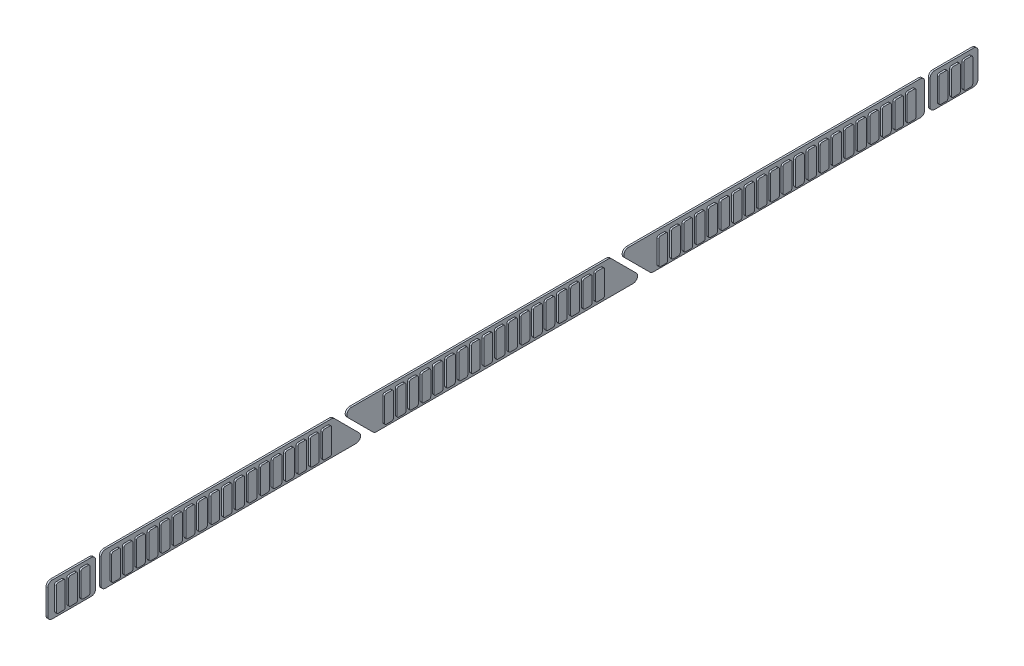
SolidWorks part; units mm, degrees
material "moto_reflective"
ref_plane "Front Plane" through (0, 0, 0) normal (0, 0, 1) x (1, 0, 0)
ref_plane "Top Plane" through (0, 0, 0) normal (0, 1, 0) x (1, 0, 0)
ref_plane "Right Plane" through (0, 0, 0) normal (1, 0, 0) x (0, 0, -1)
sketch "Sketch1" plane through (0, 0, 0) normal (1, 0, 0) x (0, 0, -1)
  line L0 (-262, -7) -> (-262, 7)
  line L5 (-237.5, 9.5) -> (-259.5, 9.5)
  line L6 (-259.5, -9.5) -> (-237.5, -9.5)
  line L8 (262, -7) -> (262, 7)
  line L10 (-232, 7) -> (-232, -7)
  line L11 (-235, 7) -> (-235, -7)
  line L12 (-76.9645, -9.5) -> (67.7218, -9.5)
  line L13 (235, 7) -> (235, -7)
  line L14 (232, 7) -> (232, -7)
  line L15 (-92.7322, 5.2322) -> (-78.7322, -8.7678)
  line L16 (63.2678, 5.2322) -> (77.2678, -8.7678)
  line L17 (-86.5104, -5.2322) -> (-100.5104, 8.7678)
  line L18 (55.4896, 8.7678) -> (69.4896, -5.2322)
  line L19 (-229.5, 9.5) -> (-102.2782, 9.5)
  line L20 (-232, 9.5) -> (-232, -9.5) construction
  line L21 (-235, 9.5) -> (-235, -9.5) construction
  line L25 (-88.2782, -9.5) -> (-229.5, -9.5)
  line L26 (-90.9645, 9.5) -> (53.7218, 9.5)
  line L27 (229.5, 9.5) -> (65.0355, 9.5)
  line L28 (79.0355, -9.5) -> (229.5, -9.5)
  line L29 (259.5, 9.5) -> (237.5, 9.5)
  line L30 (237.5, -9.5) -> (259.5, -9.5)
  line L130 (-257.1932, 7.5778) -> (-254.1932, 7.5778)
  line L131 (-258.1932, 6.5778) -> (-258.1932, -6.4222)
  line L132 (-257.1932, -7.4222) -> (-254.1932, -7.4222)
  line L133 (-253.1932, 6.5778) -> (-253.1932, -6.4222)
  line L134 (-250.1932, 7.5778) -> (-247.1932, 7.5778)
  line L135 (-251.1932, 6.5778) -> (-251.1932, -6.4222)
  line L136 (-250.1932, -7.4222) -> (-247.1932, -7.4222)
  line L137 (-246.1932, 6.5778) -> (-246.1932, -6.4222)
  line L138 (-243.1932, 7.5778) -> (-240.1932, 7.5778)
  line L139 (-244.1932, 6.5778) -> (-244.1932, -6.4222)
  line L140 (-243.1932, -7.4222) -> (-240.1932, -7.4222)
  line L141 (-239.1932, 6.5778) -> (-239.1932, -6.4222)
  line L142 (-225.9916, 7.1613) -> (-222.9916, 7.1613)
  line L143 (-226.9916, 6.1613) -> (-226.9916, -6.8387)
  line L144 (-225.9916, -7.8387) -> (-222.9916, -7.8387)
  line L145 (-221.9916, 6.1613) -> (-221.9916, -6.8387)
  line L146 (-218.9916, 7.1613) -> (-215.9916, 7.1613)
  line L147 (-219.9916, 6.1613) -> (-219.9916, -6.8387)
  line L148 (-218.9916, -7.8387) -> (-215.9916, -7.8387)
  line L149 (-214.9916, 6.1613) -> (-214.9916, -6.8387)
  line L150 (-211.9916, 7.1613) -> (-208.9916, 7.1613)
  line L151 (-212.9916, 6.1613) -> (-212.9916, -6.8387)
  line L152 (-211.9916, -7.8387) -> (-208.9916, -7.8387)
  line L153 (-207.9916, 6.1613) -> (-207.9916, -6.8387)
  line L154 (-204.9916, 7.1613) -> (-201.9916, 7.1613)
  line L155 (-205.9916, 6.1613) -> (-205.9916, -6.8387)
  line L156 (-204.9916, -7.8387) -> (-201.9916, -7.8387)
  line L157 (-200.9916, 6.1613) -> (-200.9916, -6.8387)
  line L158 (-198.1383, 7.4692) -> (-195.1383, 7.4692)
  line L159 (-199.1383, 6.4692) -> (-199.1383, -6.5308)
  line L160 (-198.1383, -7.5308) -> (-195.1383, -7.5308)
  line L161 (-194.1383, 6.4692) -> (-194.1383, -6.5308)
  line L162 (-191.1383, 7.4692) -> (-188.1383, 7.4692)
  line L163 (-192.1383, 6.4692) -> (-192.1383, -6.5308)
  line L164 (-191.1383, -7.5308) -> (-188.1383, -7.5308)
  line L165 (-187.1383, 6.4692) -> (-187.1383, -6.5308)
  line L166 (-184.1383, 7.4692) -> (-181.1383, 7.4692)
  line L167 (-185.1383, 6.4692) -> (-185.1383, -6.5308)
  line L168 (-184.1383, -7.5308) -> (-181.1383, -7.5308)
  line L169 (-180.1383, 6.4692) -> (-180.1383, -6.5308)
  line L170 (-177.1383, 7.4692) -> (-174.1383, 7.4692)
  line L171 (-178.1383, 6.4692) -> (-178.1383, -6.5308)
  line L172 (-177.1383, -7.5308) -> (-174.1383, -7.5308)
  line L173 (-173.1383, 6.4692) -> (-173.1383, -6.5308)
  line L174 (-170.1383, 7.4692) -> (-167.1383, 7.4692)
  line L175 (-171.1383, 6.4692) -> (-171.1383, -6.5308)
  line L176 (-170.1383, -7.5308) -> (-167.1383, -7.5308)
  line L177 (-166.1383, 6.4692) -> (-166.1383, -6.5308)
  line L178 (-163.1383, 7.4692) -> (-160.1383, 7.4692)
  line L179 (-164.1383, 6.4692) -> (-164.1383, -6.5308)
  line L180 (-163.1383, -7.5308) -> (-160.1383, -7.5308)
  line L181 (-159.1383, 6.4692) -> (-159.1383, -6.5308)
  line L182 (-156.1383, 7.4692) -> (-153.1383, 7.4692)
  line L183 (-157.1383, 6.4692) -> (-157.1383, -6.5308)
  line L184 (-156.1383, -7.5308) -> (-153.1383, -7.5308)
  line L185 (-152.1383, 6.4692) -> (-152.1383, -6.5308)
  line L186 (-149.1383, 7.4692) -> (-146.1383, 7.4692)
  line L187 (-150.1383, 6.4692) -> (-150.1383, -6.5308)
  line L188 (-149.1383, -7.5308) -> (-146.1383, -7.5308)
  line L189 (-145.1383, 6.4692) -> (-145.1383, -6.5308)
  line L190 (-142.1383, 7.4692) -> (-139.1383, 7.4692)
  line L191 (-143.1383, 6.4692) -> (-143.1383, -6.5308)
  line L192 (-142.1383, -7.5308) -> (-139.1383, -7.5308)
  line L193 (-138.1383, 6.4692) -> (-138.1383, -6.5308)
  line L194 (-135.1383, 7.4692) -> (-132.1383, 7.4692)
  line L195 (-136.1383, 6.4692) -> (-136.1383, -6.5308)
  line L196 (-135.1383, -7.5308) -> (-132.1383, -7.5308)
  line L197 (-131.1383, 6.4692) -> (-131.1383, -6.5308)
  line L198 (-128.1383, 7.4692) -> (-125.1383, 7.4692)
  line L199 (-129.1383, 6.4692) -> (-129.1383, -6.5308)
  line L200 (-128.1383, -7.5308) -> (-125.1383, -7.5308)
  line L201 (-124.1383, 6.4692) -> (-124.1383, -6.5308)
  line L202 (-121.1383, 7.4692) -> (-118.1383, 7.4692)
  line L203 (-122.1383, 6.4692) -> (-122.1383, -6.5308)
  line L204 (-121.1383, -7.5308) -> (-118.1383, -7.5308)
  line L205 (-117.1383, 6.4692) -> (-117.1383, -6.5308)
  line L206 (-114.1383, 7.4692) -> (-111.1383, 7.4692)
  line L207 (-115.1383, 6.4692) -> (-115.1383, -6.5308)
  line L208 (-114.1383, -7.5308) -> (-111.1383, -7.5308)
  line L209 (-110.1383, 6.4692) -> (-110.1383, -6.5308)
  line L210 (-107.1383, 7.4692) -> (-104.1383, 7.4692)
  line L211 (-108.1383, 6.4692) -> (-108.1383, -6.5308)
  line L212 (-107.1383, -7.5308) -> (-104.1383, -7.5308)
  line L213 (-103.1383, 6.4692) -> (-103.1383, -6.5308)
  line L222 (-72.2636, 7.3699) -> (-69.2636, 7.3699)
  line L223 (-73.2636, 6.3699) -> (-73.2636, -6.6301)
  line L224 (-72.2636, -7.6301) -> (-69.2636, -7.6301)
  line L225 (-68.2636, 6.3699) -> (-68.2636, -6.6301)
  line L226 (-65.2636, 7.3699) -> (-62.2636, 7.3699)
  line L227 (-66.2636, 6.3699) -> (-66.2636, -6.6301)
  line L228 (-65.2636, -7.6301) -> (-62.2636, -7.6301)
  line L229 (-61.2636, 6.3699) -> (-61.2636, -6.6301)
  line L230 (-58.2636, 7.3699) -> (-55.2636, 7.3699)
  line L231 (-59.2636, 6.3699) -> (-59.2636, -6.6301)
  line L232 (-58.2636, -7.6301) -> (-55.2636, -7.6301)
  line L233 (-54.2636, 6.3699) -> (-54.2636, -6.6301)
  line L234 (-51.2636, 7.3699) -> (-48.2636, 7.3699)
  line L235 (-52.2636, 6.3699) -> (-52.2636, -6.6301)
  line L236 (-51.2636, -7.6301) -> (-48.2636, -7.6301)
  line L237 (-47.2636, 6.3699) -> (-47.2636, -6.6301)
  line L238 (-44.4103, 7.6778) -> (-41.4103, 7.6778)
  line L239 (-45.4103, 6.6778) -> (-45.4103, -6.3222)
  line L240 (-44.4103, -7.3222) -> (-41.4103, -7.3222)
  line L241 (-40.4103, 6.6778) -> (-40.4103, -6.3222)
  line L242 (-37.4103, 7.6778) -> (-34.4103, 7.6778)
  line L243 (-38.4103, 6.6778) -> (-38.4103, -6.3222)
  line L244 (-37.4103, -7.3222) -> (-34.4103, -7.3222)
  line L245 (-33.4103, 6.6778) -> (-33.4103, -6.3222)
  line L246 (-30.4103, 7.6778) -> (-27.4103, 7.6778)
  line L247 (-31.4103, 6.6778) -> (-31.4103, -6.3222)
  line L248 (-30.4103, -7.3222) -> (-27.4103, -7.3222)
  line L249 (-26.4103, 6.6778) -> (-26.4103, -6.3222)
  line L250 (-23.4103, 7.6778) -> (-20.4103, 7.6778)
  line L251 (-24.4103, 6.6778) -> (-24.4103, -6.3222)
  line L252 (-23.4103, -7.3222) -> (-20.4103, -7.3222)
  line L253 (-19.4103, 6.6778) -> (-19.4103, -6.3222)
  line L254 (-16.4103, 7.6778) -> (-13.4103, 7.6778)
  line L255 (-17.4103, 6.6778) -> (-17.4103, -6.3222)
  line L256 (-16.4103, -7.3222) -> (-13.4103, -7.3222)
  line L257 (-12.4103, 6.6778) -> (-12.4103, -6.3222)
  line L258 (-9.4103, 7.6778) -> (-6.4103, 7.6778)
  line L259 (-10.4103, 6.6778) -> (-10.4103, -6.3222)
  line L260 (-9.4103, -7.3222) -> (-6.4103, -7.3222)
  line L261 (-5.4103, 6.6778) -> (-5.4103, -6.3222)
  line L262 (-2.4103, 7.6778) -> (0.5897, 7.6778)
  line L263 (-3.4103, 6.6778) -> (-3.4103, -6.3222)
  line L264 (-2.4103, -7.3222) -> (0.5897, -7.3222)
  line L265 (1.5897, 6.6778) -> (1.5897, -6.3222)
  line L266 (4.5897, 7.6778) -> (7.5897, 7.6778)
  line L267 (3.5897, 6.6778) -> (3.5897, -6.3222)
  line L268 (4.5897, -7.3222) -> (7.5897, -7.3222)
  line L269 (8.5897, 6.6778) -> (8.5897, -6.3222)
  line L270 (11.5897, 7.6778) -> (14.5897, 7.6778)
  line L271 (10.5897, 6.6778) -> (10.5897, -6.3222)
  line L272 (11.5897, -7.3222) -> (14.5897, -7.3222)
  line L273 (15.5897, 6.6778) -> (15.5897, -6.3222)
  line L274 (18.5897, 7.6778) -> (21.5897, 7.6778)
  line L275 (17.5897, 6.6778) -> (17.5897, -6.3222)
  line L276 (18.5897, -7.3222) -> (21.5897, -7.3222)
  line L277 (22.5897, 6.6778) -> (22.5897, -6.3222)
  line L278 (25.5897, 7.6778) -> (28.5897, 7.6778)
  line L279 (24.5897, 6.6778) -> (24.5897, -6.3222)
  line L280 (25.5897, -7.3222) -> (28.5897, -7.3222)
  line L281 (29.5897, 6.6778) -> (29.5897, -6.3222)
  line L282 (32.5897, 7.6778) -> (35.5897, 7.6778)
  line L283 (31.5897, 6.6778) -> (31.5897, -6.3222)
  line L284 (32.5897, -7.3222) -> (35.5897, -7.3222)
  line L285 (36.5897, 6.6778) -> (36.5897, -6.3222)
  line L286 (39.5897, 7.6778) -> (42.5897, 7.6778)
  line L287 (38.5897, 6.6778) -> (38.5897, -6.3222)
  line L288 (39.5897, -7.3222) -> (42.5897, -7.3222)
  line L289 (43.5897, 6.6778) -> (43.5897, -6.3222)
  line L290 (46.5897, 7.6778) -> (49.5897, 7.6778)
  line L291 (45.5897, 6.6778) -> (45.5897, -6.3222)
  line L292 (46.5897, -7.3222) -> (49.5897, -7.3222)
  line L293 (50.5897, 6.6778) -> (50.5897, -6.3222)
  line L366 (89.284, 7.2213) -> (92.284, 7.2213)
  line L367 (88.284, 6.2213) -> (88.284, -6.7787)
  line L368 (89.284, -7.7787) -> (92.284, -7.7787)
  line L369 (93.284, 6.2213) -> (93.284, -6.7787)
  line L370 (96.284, 7.2213) -> (99.284, 7.2213)
  line L371 (95.284, 6.2213) -> (95.284, -6.7787)
  line L372 (96.284, -7.7787) -> (99.284, -7.7787)
  line L373 (100.284, 6.2213) -> (100.284, -6.7787)
  line L374 (103.284, 7.2213) -> (106.284, 7.2213)
  line L375 (102.284, 6.2213) -> (102.284, -6.7787)
  line L376 (103.284, -7.7787) -> (106.284, -7.7787)
  line L377 (107.284, 6.2213) -> (107.284, -6.7787)
  line L378 (110.284, 7.2213) -> (113.284, 7.2213)
  line L379 (109.284, 6.2213) -> (109.284, -6.7787)
  line L380 (110.284, -7.7787) -> (113.284, -7.7787)
  line L381 (114.284, 6.2213) -> (114.284, -6.7787)
  line L382 (117.1373, 7.2213) -> (120.1373, 7.2213)
  line L383 (116.1373, 6.2213) -> (116.1373, -6.7787)
  line L384 (117.1373, -7.7787) -> (120.1373, -7.7787)
  line L385 (121.1373, 6.2213) -> (121.1373, -6.7787)
  line L386 (124.1373, 7.2213) -> (127.1373, 7.2213)
  line L387 (123.1373, 6.2213) -> (123.1373, -6.7787)
  line L388 (124.1373, -7.7787) -> (127.1373, -7.7787)
  line L389 (128.1373, 6.2213) -> (128.1373, -6.7787)
  line L390 (131.1373, 7.2213) -> (134.1373, 7.2213)
  line L391 (130.1373, 6.2213) -> (130.1373, -6.7787)
  line L392 (131.1373, -7.7787) -> (134.1373, -7.7787)
  line L393 (135.1373, 6.2213) -> (135.1373, -6.7787)
  line L394 (138.1373, 7.2213) -> (141.1373, 7.2213)
  line L395 (137.1373, 6.2213) -> (137.1373, -6.7787)
  line L396 (138.1373, -7.7787) -> (141.1373, -7.7787)
  line L397 (142.1373, 6.2213) -> (142.1373, -6.7787)
  line L398 (145.1373, 7.2213) -> (148.1373, 7.2213)
  line L399 (144.1373, 6.2213) -> (144.1373, -6.7787)
  line L400 (145.1373, -7.7787) -> (148.1373, -7.7787)
  line L401 (149.1373, 6.2213) -> (149.1373, -6.7787)
  line L402 (152.1373, 7.2213) -> (155.1373, 7.2213)
  line L403 (151.1373, 6.2213) -> (151.1373, -6.7787)
  line L404 (152.1373, -7.7787) -> (155.1373, -7.7787)
  line L405 (156.1373, 6.2213) -> (156.1373, -6.7787)
  line L406 (159.1373, 7.2213) -> (162.1373, 7.2213)
  line L407 (158.1373, 6.2213) -> (158.1373, -6.7787)
  line L408 (159.1373, -7.7787) -> (162.1373, -7.7787)
  line L409 (163.1373, 6.2213) -> (163.1373, -6.7787)
  line L410 (166.1373, 7.2213) -> (169.1373, 7.2213)
  line L411 (165.1373, 6.2213) -> (165.1373, -6.7787)
  line L412 (166.1373, -7.7787) -> (169.1373, -7.7787)
  line L413 (170.1373, 6.2213) -> (170.1373, -6.7787)
  line L414 (173.1373, 7.2213) -> (176.1373, 7.2213)
  line L415 (172.1373, 6.2213) -> (172.1373, -6.7787)
  line L416 (173.1373, -7.7787) -> (176.1373, -7.7787)
  line L417 (177.1373, 6.2213) -> (177.1373, -6.7787)
  line L418 (180.1373, 7.2213) -> (183.1373, 7.2213)
  line L419 (179.1373, 6.2213) -> (179.1373, -6.7787)
  line L420 (180.1373, -7.7787) -> (183.1373, -7.7787)
  line L421 (184.1373, 6.2213) -> (184.1373, -6.7787)
  line L422 (187.1373, 7.2213) -> (190.1373, 7.2213)
  line L423 (186.1373, 6.2213) -> (186.1373, -6.7787)
  line L424 (187.1373, -7.7787) -> (190.1373, -7.7787)
  line L425 (191.1373, 6.2213) -> (191.1373, -6.7787)
  line L426 (194.1373, 7.2213) -> (197.1373, 7.2213)
  line L427 (193.1373, 6.2213) -> (193.1373, -6.7787)
  line L428 (194.1373, -7.7787) -> (197.1373, -7.7787)
  line L429 (198.1373, 6.2213) -> (198.1373, -6.7787)
  line L430 (201.1373, 7.2213) -> (204.1373, 7.2213)
  line L431 (200.1373, 6.2213) -> (200.1373, -6.7787)
  line L432 (201.1373, -7.7787) -> (204.1373, -7.7787)
  line L433 (205.1373, 6.2213) -> (205.1373, -6.7787)
  line L434 (208.1373, 7.2213) -> (211.1373, 7.2213)
  line L435 (207.1373, 6.2213) -> (207.1373, -6.7787)
  line L436 (208.1373, -7.7787) -> (211.1373, -7.7787)
  line L437 (212.1373, 6.2213) -> (212.1373, -6.7787)
  line L438 (215.1373, 7.2213) -> (218.1373, 7.2213)
  line L439 (214.1373, 6.2213) -> (214.1373, -6.7787)
  line L440 (215.1373, -7.7787) -> (218.1373, -7.7787)
  line L441 (219.1373, 6.2213) -> (219.1373, -6.7787)
  line L442 (222.1373, 7.2213) -> (225.1373, 7.2213)
  line L443 (221.1373, 6.2213) -> (221.1373, -6.7787)
  line L444 (222.1373, -7.7787) -> (225.1373, -7.7787)
  line L445 (226.1373, 6.2213) -> (226.1373, -6.7787)
  line L446 (240.0473, 7.2253) -> (243.0473, 7.2253)
  line L447 (239.0473, 6.2253) -> (239.0473, -6.7747)
  line L448 (240.0473, -7.7747) -> (243.0473, -7.7747)
  line L449 (244.0473, 6.2253) -> (244.0473, -6.7747)
  line L450 (247.0473, 7.2253) -> (250.0473, 7.2253)
  line L451 (246.0473, 6.2253) -> (246.0473, -6.7747)
  line L452 (247.0473, -7.7747) -> (250.0473, -7.7747)
  line L453 (251.0473, 6.2253) -> (251.0473, -6.7747)
  line L454 (254.0473, 7.2253) -> (257.0473, 7.2253)
  line L455 (253.0473, 6.2253) -> (253.0473, -6.7747)
  line L456 (254.0473, -7.7747) -> (257.0473, -7.7747)
  line L457 (258.0473, 6.2253) -> (258.0473, -6.7747)
  line L458 (82.1912, 7.0408) -> (85.1912, 7.0408)
  line L459 (81.1912, 6.0408) -> (81.1912, -6.9592)
  line L460 (82.1912, -7.9592) -> (85.1912, -7.9592)
  line L461 (86.1912, 6.0408) -> (86.1912, -6.9592)
  arc A0 (69.4896, -5.2322) -> (67.7218, -9.5) centre (67.7218, -7) cw
  arc A1 (55.4896, 8.7678) -> (53.7218, 9.5) centre (53.7218, 7) ccw
  arc A2 (-100.5104, 8.7678) -> (-102.2782, 9.5) centre (-102.2782, 7) ccw
  arc A3 (-86.5104, -5.2322) -> (-88.2782, -9.5) centre (-88.2782, -7) cw
  arc A4 (77.2678, -8.7678) -> (79.0355, -9.5) centre (79.0355, -7) ccw
  arc A5 (63.2678, 5.2322) -> (65.0355, 9.5) centre (65.0355, 7) cw
  arc A6 (-78.7322, -8.7678) -> (-76.9645, -9.5) centre (-76.9645, -7) ccw
  arc A7 (-92.7322, 5.2322) -> (-90.9645, 9.5) centre (-90.9645, 7) cw
  arc A8 (232, -7) -> (229.5, -9.5) centre (229.5, -7) cw
  arc A9 (232, 7) -> (229.5, 9.5) centre (229.5, 7) ccw
  arc A10 (235, -7) -> (237.5, -9.5) centre (237.5, -7) ccw
  arc A11 (235, 7) -> (237.5, 9.5) centre (237.5, 7) cw
  arc A12 (-232, -7) -> (-229.5, -9.5) centre (-229.5, -7) ccw
  arc A13 (-232, 7) -> (-229.5, 9.5) centre (-229.5, 7) cw
  arc A14 (262, -7) -> (259.5, -9.5) centre (259.5, -7) cw
  arc A15 (259.5, 9.5) -> (262, 7) centre (259.5, 7) cw
  arc A16 (-235, -7) -> (-237.5, -9.5) centre (-237.5, -7) cw
  arc A17 (-235, 7) -> (-237.5, 9.5) centre (-237.5, 7) ccw
  arc A18 (-262, 7) -> (-259.5, 9.5) centre (-259.5, 7) cw
  arc A19 (-262, -7) -> (-259.5, -9.5) centre (-259.5, -7) ccw
  arc A116 (-258.1932, -6.4222) -> (-257.1932, -7.4222) centre (-257.1932, -6.4222) ccw
  arc A117 (-254.1932, -7.4222) -> (-253.1932, -6.4222) centre (-254.1932, -6.4222) ccw
  arc A118 (-254.1932, 7.5778) -> (-253.1932, 6.5778) centre (-254.1932, 6.5778) cw
  arc A119 (-257.1932, 7.5778) -> (-258.1932, 6.5778) centre (-257.1932, 6.5778) ccw
  arc A120 (-251.1932, -6.4222) -> (-250.1932, -7.4222) centre (-250.1932, -6.4222) ccw
  arc A121 (-247.1932, -7.4222) -> (-246.1932, -6.4222) centre (-247.1932, -6.4222) ccw
  arc A122 (-247.1932, 7.5778) -> (-246.1932, 6.5778) centre (-247.1932, 6.5778) cw
  arc A123 (-250.1932, 7.5778) -> (-251.1932, 6.5778) centre (-250.1932, 6.5778) ccw
  arc A124 (-244.1932, -6.4222) -> (-243.1932, -7.4222) centre (-243.1932, -6.4222) ccw
  arc A125 (-240.1932, -7.4222) -> (-239.1932, -6.4222) centre (-240.1932, -6.4222) ccw
  arc A126 (-240.1932, 7.5778) -> (-239.1932, 6.5778) centre (-240.1932, 6.5778) cw
  arc A127 (-243.1932, 7.5778) -> (-244.1932, 6.5778) centre (-243.1932, 6.5778) ccw
  arc A128 (-226.9916, -6.8387) -> (-225.9916, -7.8387) centre (-225.9916, -6.8387) ccw
  arc A129 (-222.9916, -7.8387) -> (-221.9916, -6.8387) centre (-222.9916, -6.8387) ccw
  arc A130 (-222.9916, 7.1613) -> (-221.9916, 6.1613) centre (-222.9916, 6.1613) cw
  arc A131 (-225.9916, 7.1613) -> (-226.9916, 6.1613) centre (-225.9916, 6.1613) ccw
  arc A132 (-219.9916, -6.8387) -> (-218.9916, -7.8387) centre (-218.9916, -6.8387) ccw
  arc A133 (-215.9916, -7.8387) -> (-214.9916, -6.8387) centre (-215.9916, -6.8387) ccw
  arc A134 (-215.9916, 7.1613) -> (-214.9916, 6.1613) centre (-215.9916, 6.1613) cw
  arc A135 (-218.9916, 7.1613) -> (-219.9916, 6.1613) centre (-218.9916, 6.1613) ccw
  arc A136 (-212.9916, -6.8387) -> (-211.9916, -7.8387) centre (-211.9916, -6.8387) ccw
  arc A137 (-208.9916, -7.8387) -> (-207.9916, -6.8387) centre (-208.9916, -6.8387) ccw
  arc A138 (-208.9916, 7.1613) -> (-207.9916, 6.1613) centre (-208.9916, 6.1613) cw
  arc A139 (-211.9916, 7.1613) -> (-212.9916, 6.1613) centre (-211.9916, 6.1613) ccw
  arc A140 (-205.9916, -6.8387) -> (-204.9916, -7.8387) centre (-204.9916, -6.8387) ccw
  arc A141 (-201.9916, -7.8387) -> (-200.9916, -6.8387) centre (-201.9916, -6.8387) ccw
  arc A142 (-201.9916, 7.1613) -> (-200.9916, 6.1613) centre (-201.9916, 6.1613) cw
  arc A143 (-204.9916, 7.1613) -> (-205.9916, 6.1613) centre (-204.9916, 6.1613) ccw
  arc A144 (-199.1383, -6.5308) -> (-198.1383, -7.5308) centre (-198.1383, -6.5308) ccw
  arc A145 (-195.1383, -7.5308) -> (-194.1383, -6.5308) centre (-195.1383, -6.5308) ccw
  arc A146 (-195.1383, 7.4692) -> (-194.1383, 6.4692) centre (-195.1383, 6.4692) cw
  arc A147 (-198.1383, 7.4692) -> (-199.1383, 6.4692) centre (-198.1383, 6.4692) ccw
  arc A148 (-192.1383, -6.5308) -> (-191.1383, -7.5308) centre (-191.1383, -6.5308) ccw
  arc A149 (-188.1383, -7.5308) -> (-187.1383, -6.5308) centre (-188.1383, -6.5308) ccw
  arc A150 (-188.1383, 7.4692) -> (-187.1383, 6.4692) centre (-188.1383, 6.4692) cw
  arc A151 (-191.1383, 7.4692) -> (-192.1383, 6.4692) centre (-191.1383, 6.4692) ccw
  arc A152 (-185.1383, -6.5308) -> (-184.1383, -7.5308) centre (-184.1383, -6.5308) ccw
  arc A153 (-181.1383, -7.5308) -> (-180.1383, -6.5308) centre (-181.1383, -6.5308) ccw
  arc A154 (-181.1383, 7.4692) -> (-180.1383, 6.4692) centre (-181.1383, 6.4692) cw
  arc A155 (-184.1383, 7.4692) -> (-185.1383, 6.4692) centre (-184.1383, 6.4692) ccw
  arc A156 (-178.1383, -6.5308) -> (-177.1383, -7.5308) centre (-177.1383, -6.5308) ccw
  arc A157 (-174.1383, -7.5308) -> (-173.1383, -6.5308) centre (-174.1383, -6.5308) ccw
  arc A158 (-174.1383, 7.4692) -> (-173.1383, 6.4692) centre (-174.1383, 6.4692) cw
  arc A159 (-177.1383, 7.4692) -> (-178.1383, 6.4692) centre (-177.1383, 6.4692) ccw
  arc A160 (-171.1383, -6.5308) -> (-170.1383, -7.5308) centre (-170.1383, -6.5308) ccw
  arc A161 (-167.1383, -7.5308) -> (-166.1383, -6.5308) centre (-167.1383, -6.5308) ccw
  arc A162 (-167.1383, 7.4692) -> (-166.1383, 6.4692) centre (-167.1383, 6.4692) cw
  arc A163 (-170.1383, 7.4692) -> (-171.1383, 6.4692) centre (-170.1383, 6.4692) ccw
  arc A164 (-164.1383, -6.5308) -> (-163.1383, -7.5308) centre (-163.1383, -6.5308) ccw
  arc A165 (-160.1383, -7.5308) -> (-159.1383, -6.5308) centre (-160.1383, -6.5308) ccw
  arc A166 (-160.1383, 7.4692) -> (-159.1383, 6.4692) centre (-160.1383, 6.4692) cw
  arc A167 (-163.1383, 7.4692) -> (-164.1383, 6.4692) centre (-163.1383, 6.4692) ccw
  arc A168 (-157.1383, -6.5308) -> (-156.1383, -7.5308) centre (-156.1383, -6.5308) ccw
  arc A169 (-153.1383, -7.5308) -> (-152.1383, -6.5308) centre (-153.1383, -6.5308) ccw
  arc A170 (-153.1383, 7.4692) -> (-152.1383, 6.4692) centre (-153.1383, 6.4692) cw
  arc A171 (-156.1383, 7.4692) -> (-157.1383, 6.4692) centre (-156.1383, 6.4692) ccw
  arc A172 (-150.1383, -6.5308) -> (-149.1383, -7.5308) centre (-149.1383, -6.5308) ccw
  arc A173 (-146.1383, -7.5308) -> (-145.1383, -6.5308) centre (-146.1383, -6.5308) ccw
  arc A174 (-146.1383, 7.4692) -> (-145.1383, 6.4692) centre (-146.1383, 6.4692) cw
  arc A175 (-149.1383, 7.4692) -> (-150.1383, 6.4692) centre (-149.1383, 6.4692) ccw
  arc A176 (-143.1383, -6.5308) -> (-142.1383, -7.5308) centre (-142.1383, -6.5308) ccw
  arc A177 (-139.1383, -7.5308) -> (-138.1383, -6.5308) centre (-139.1383, -6.5308) ccw
  arc A178 (-139.1383, 7.4692) -> (-138.1383, 6.4692) centre (-139.1383, 6.4692) cw
  arc A179 (-142.1383, 7.4692) -> (-143.1383, 6.4692) centre (-142.1383, 6.4692) ccw
  arc A180 (-136.1383, -6.5308) -> (-135.1383, -7.5308) centre (-135.1383, -6.5308) ccw
  arc A181 (-132.1383, -7.5308) -> (-131.1383, -6.5308) centre (-132.1383, -6.5308) ccw
  arc A182 (-132.1383, 7.4692) -> (-131.1383, 6.4692) centre (-132.1383, 6.4692) cw
  arc A183 (-135.1383, 7.4692) -> (-136.1383, 6.4692) centre (-135.1383, 6.4692) ccw
  arc A184 (-129.1383, -6.5308) -> (-128.1383, -7.5308) centre (-128.1383, -6.5308) ccw
  arc A185 (-125.1383, -7.5308) -> (-124.1383, -6.5308) centre (-125.1383, -6.5308) ccw
  arc A186 (-125.1383, 7.4692) -> (-124.1383, 6.4692) centre (-125.1383, 6.4692) cw
  arc A187 (-128.1383, 7.4692) -> (-129.1383, 6.4692) centre (-128.1383, 6.4692) ccw
  arc A188 (-122.1383, -6.5308) -> (-121.1383, -7.5308) centre (-121.1383, -6.5308) ccw
  arc A189 (-118.1383, -7.5308) -> (-117.1383, -6.5308) centre (-118.1383, -6.5308) ccw
  arc A190 (-118.1383, 7.4692) -> (-117.1383, 6.4692) centre (-118.1383, 6.4692) cw
  arc A191 (-121.1383, 7.4692) -> (-122.1383, 6.4692) centre (-121.1383, 6.4692) ccw
  arc A192 (-115.1383, -6.5308) -> (-114.1383, -7.5308) centre (-114.1383, -6.5308) ccw
  arc A193 (-111.1383, -7.5308) -> (-110.1383, -6.5308) centre (-111.1383, -6.5308) ccw
  arc A194 (-111.1383, 7.4692) -> (-110.1383, 6.4692) centre (-111.1383, 6.4692) cw
  arc A195 (-114.1383, 7.4692) -> (-115.1383, 6.4692) centre (-114.1383, 6.4692) ccw
  arc A196 (-108.1383, -6.5308) -> (-107.1383, -7.5308) centre (-107.1383, -6.5308) ccw
  arc A197 (-104.1383, -7.5308) -> (-103.1383, -6.5308) centre (-104.1383, -6.5308) ccw
  arc A198 (-104.1383, 7.4692) -> (-103.1383, 6.4692) centre (-104.1383, 6.4692) cw
  arc A199 (-107.1383, 7.4692) -> (-108.1383, 6.4692) centre (-107.1383, 6.4692) ccw
  arc A208 (-73.2636, -6.6301) -> (-72.2636, -7.6301) centre (-72.2636, -6.6301) ccw
  arc A209 (-69.2636, -7.6301) -> (-68.2636, -6.6301) centre (-69.2636, -6.6301) ccw
  arc A210 (-69.2636, 7.3699) -> (-68.2636, 6.3699) centre (-69.2636, 6.3699) cw
  arc A211 (-72.2636, 7.3699) -> (-73.2636, 6.3699) centre (-72.2636, 6.3699) ccw
  arc A212 (-66.2636, -6.6301) -> (-65.2636, -7.6301) centre (-65.2636, -6.6301) ccw
  arc A213 (-62.2636, -7.6301) -> (-61.2636, -6.6301) centre (-62.2636, -6.6301) ccw
  arc A214 (-62.2636, 7.3699) -> (-61.2636, 6.3699) centre (-62.2636, 6.3699) cw
  arc A215 (-65.2636, 7.3699) -> (-66.2636, 6.3699) centre (-65.2636, 6.3699) ccw
  arc A216 (-59.2636, -6.6301) -> (-58.2636, -7.6301) centre (-58.2636, -6.6301) ccw
  arc A217 (-55.2636, -7.6301) -> (-54.2636, -6.6301) centre (-55.2636, -6.6301) ccw
  arc A218 (-55.2636, 7.3699) -> (-54.2636, 6.3699) centre (-55.2636, 6.3699) cw
  arc A219 (-58.2636, 7.3699) -> (-59.2636, 6.3699) centre (-58.2636, 6.3699) ccw
  arc A220 (-52.2636, -6.6301) -> (-51.2636, -7.6301) centre (-51.2636, -6.6301) ccw
  arc A221 (-48.2636, -7.6301) -> (-47.2636, -6.6301) centre (-48.2636, -6.6301) ccw
  arc A222 (-48.2636, 7.3699) -> (-47.2636, 6.3699) centre (-48.2636, 6.3699) cw
  arc A223 (-51.2636, 7.3699) -> (-52.2636, 6.3699) centre (-51.2636, 6.3699) ccw
  arc A224 (-45.4103, -6.3222) -> (-44.4103, -7.3222) centre (-44.4103, -6.3222) ccw
  arc A225 (-41.4103, -7.3222) -> (-40.4103, -6.3222) centre (-41.4103, -6.3222) ccw
  arc A226 (-41.4103, 7.6778) -> (-40.4103, 6.6778) centre (-41.4103, 6.6778) cw
  arc A227 (-44.4103, 7.6778) -> (-45.4103, 6.6778) centre (-44.4103, 6.6778) ccw
  arc A228 (-38.4103, -6.3222) -> (-37.4103, -7.3222) centre (-37.4103, -6.3222) ccw
  arc A229 (-34.4103, -7.3222) -> (-33.4103, -6.3222) centre (-34.4103, -6.3222) ccw
  arc A230 (-34.4103, 7.6778) -> (-33.4103, 6.6778) centre (-34.4103, 6.6778) cw
  arc A231 (-37.4103, 7.6778) -> (-38.4103, 6.6778) centre (-37.4103, 6.6778) ccw
  arc A232 (-31.4103, -6.3222) -> (-30.4103, -7.3222) centre (-30.4103, -6.3222) ccw
  arc A233 (-27.4103, -7.3222) -> (-26.4103, -6.3222) centre (-27.4103, -6.3222) ccw
  arc A234 (-27.4103, 7.6778) -> (-26.4103, 6.6778) centre (-27.4103, 6.6778) cw
  arc A235 (-30.4103, 7.6778) -> (-31.4103, 6.6778) centre (-30.4103, 6.6778) ccw
  arc A236 (-24.4103, -6.3222) -> (-23.4103, -7.3222) centre (-23.4103, -6.3222) ccw
  arc A237 (-20.4103, -7.3222) -> (-19.4103, -6.3222) centre (-20.4103, -6.3222) ccw
  arc A238 (-20.4103, 7.6778) -> (-19.4103, 6.6778) centre (-20.4103, 6.6778) cw
  arc A239 (-23.4103, 7.6778) -> (-24.4103, 6.6778) centre (-23.4103, 6.6778) ccw
  arc A240 (-17.4103, -6.3222) -> (-16.4103, -7.3222) centre (-16.4103, -6.3222) ccw
  arc A241 (-13.4103, -7.3222) -> (-12.4103, -6.3222) centre (-13.4103, -6.3222) ccw
  arc A242 (-13.4103, 7.6778) -> (-12.4103, 6.6778) centre (-13.4103, 6.6778) cw
  arc A243 (-16.4103, 7.6778) -> (-17.4103, 6.6778) centre (-16.4103, 6.6778) ccw
  arc A244 (-10.4103, -6.3222) -> (-9.4103, -7.3222) centre (-9.4103, -6.3222) ccw
  arc A245 (-6.4103, -7.3222) -> (-5.4103, -6.3222) centre (-6.4103, -6.3222) ccw
  arc A246 (-6.4103, 7.6778) -> (-5.4103, 6.6778) centre (-6.4103, 6.6778) cw
  arc A247 (-9.4103, 7.6778) -> (-10.4103, 6.6778) centre (-9.4103, 6.6778) ccw
  arc A248 (-3.4103, -6.3222) -> (-2.4103, -7.3222) centre (-2.4103, -6.3222) ccw
  arc A249 (0.5897, -7.3222) -> (1.5897, -6.3222) centre (0.5897, -6.3222) ccw
  arc A250 (0.5897, 7.6778) -> (1.5897, 6.6778) centre (0.5897, 6.6778) cw
  arc A251 (-2.4103, 7.6778) -> (-3.4103, 6.6778) centre (-2.4103, 6.6778) ccw
  arc A252 (3.5897, -6.3222) -> (4.5897, -7.3222) centre (4.5897, -6.3222) ccw
  arc A253 (7.5897, -7.3222) -> (8.5897, -6.3222) centre (7.5897, -6.3222) ccw
  arc A254 (7.5897, 7.6778) -> (8.5897, 6.6778) centre (7.5897, 6.6778) cw
  arc A255 (4.5897, 7.6778) -> (3.5897, 6.6778) centre (4.5897, 6.6778) ccw
  arc A256 (10.5897, -6.3222) -> (11.5897, -7.3222) centre (11.5897, -6.3222) ccw
  arc A257 (14.5897, -7.3222) -> (15.5897, -6.3222) centre (14.5897, -6.3222) ccw
  arc A258 (14.5897, 7.6778) -> (15.5897, 6.6778) centre (14.5897, 6.6778) cw
  arc A259 (11.5897, 7.6778) -> (10.5897, 6.6778) centre (11.5897, 6.6778) ccw
  arc A260 (17.5897, -6.3222) -> (18.5897, -7.3222) centre (18.5897, -6.3222) ccw
  arc A261 (21.5897, -7.3222) -> (22.5897, -6.3222) centre (21.5897, -6.3222) ccw
  arc A262 (21.5897, 7.6778) -> (22.5897, 6.6778) centre (21.5897, 6.6778) cw
  arc A263 (18.5897, 7.6778) -> (17.5897, 6.6778) centre (18.5897, 6.6778) ccw
  arc A264 (24.5897, -6.3222) -> (25.5897, -7.3222) centre (25.5897, -6.3222) ccw
  arc A265 (28.5897, -7.3222) -> (29.5897, -6.3222) centre (28.5897, -6.3222) ccw
  arc A266 (28.5897, 7.6778) -> (29.5897, 6.6778) centre (28.5897, 6.6778) cw
  arc A267 (25.5897, 7.6778) -> (24.5897, 6.6778) centre (25.5897, 6.6778) ccw
  arc A268 (31.5897, -6.3222) -> (32.5897, -7.3222) centre (32.5897, -6.3222) ccw
  arc A269 (35.5897, -7.3222) -> (36.5897, -6.3222) centre (35.5897, -6.3222) ccw
  arc A270 (35.5897, 7.6778) -> (36.5897, 6.6778) centre (35.5897, 6.6778) cw
  arc A271 (32.5897, 7.6778) -> (31.5897, 6.6778) centre (32.5897, 6.6778) ccw
  arc A272 (38.5897, -6.3222) -> (39.5897, -7.3222) centre (39.5897, -6.3222) ccw
  arc A273 (42.5897, -7.3222) -> (43.5897, -6.3222) centre (42.5897, -6.3222) ccw
  arc A274 (42.5897, 7.6778) -> (43.5897, 6.6778) centre (42.5897, 6.6778) cw
  arc A275 (39.5897, 7.6778) -> (38.5897, 6.6778) centre (39.5897, 6.6778) ccw
  arc A276 (45.5897, -6.3222) -> (46.5897, -7.3222) centre (46.5897, -6.3222) ccw
  arc A277 (49.5897, -7.3222) -> (50.5897, -6.3222) centre (49.5897, -6.3222) ccw
  arc A278 (49.5897, 7.6778) -> (50.5897, 6.6778) centre (49.5897, 6.6778) cw
  arc A279 (46.5897, 7.6778) -> (45.5897, 6.6778) centre (46.5897, 6.6778) ccw
  arc A352 (88.284, -6.7787) -> (89.284, -7.7787) centre (89.284, -6.7787) ccw
  arc A353 (92.284, -7.7787) -> (93.284, -6.7787) centre (92.284, -6.7787) ccw
  arc A354 (92.284, 7.2213) -> (93.284, 6.2213) centre (92.284, 6.2213) cw
  arc A355 (89.284, 7.2213) -> (88.284, 6.2213) centre (89.284, 6.2213) ccw
  arc A356 (95.284, -6.7787) -> (96.284, -7.7787) centre (96.284, -6.7787) ccw
  arc A357 (99.284, -7.7787) -> (100.284, -6.7787) centre (99.284, -6.7787) ccw
  arc A358 (99.284, 7.2213) -> (100.284, 6.2213) centre (99.284, 6.2213) cw
  arc A359 (96.284, 7.2213) -> (95.284, 6.2213) centre (96.284, 6.2213) ccw
  arc A360 (102.284, -6.7787) -> (103.284, -7.7787) centre (103.284, -6.7787) ccw
  arc A361 (106.284, -7.7787) -> (107.284, -6.7787) centre (106.284, -6.7787) ccw
  arc A362 (106.284, 7.2213) -> (107.284, 6.2213) centre (106.284, 6.2213) cw
  arc A363 (103.284, 7.2213) -> (102.284, 6.2213) centre (103.284, 6.2213) ccw
  arc A364 (109.284, -6.7787) -> (110.284, -7.7787) centre (110.284, -6.7787) ccw
  arc A365 (113.284, -7.7787) -> (114.284, -6.7787) centre (113.284, -6.7787) ccw
  arc A366 (113.284, 7.2213) -> (114.284, 6.2213) centre (113.284, 6.2213) cw
  arc A367 (110.284, 7.2213) -> (109.284, 6.2213) centre (110.284, 6.2213) ccw
  arc A368 (116.1373, -6.7787) -> (117.1373, -7.7787) centre (117.1373, -6.7787) ccw
  arc A369 (120.1373, -7.7787) -> (121.1373, -6.7787) centre (120.1373, -6.7787) ccw
  arc A370 (120.1373, 7.2213) -> (121.1373, 6.2213) centre (120.1373, 6.2213) cw
  arc A371 (117.1373, 7.2213) -> (116.1373, 6.2213) centre (117.1373, 6.2213) ccw
  arc A372 (123.1373, -6.7787) -> (124.1373, -7.7787) centre (124.1373, -6.7787) ccw
  arc A373 (127.1373, -7.7787) -> (128.1373, -6.7787) centre (127.1373, -6.7787) ccw
  arc A374 (127.1373, 7.2213) -> (128.1373, 6.2213) centre (127.1373, 6.2213) cw
  arc A375 (124.1373, 7.2213) -> (123.1373, 6.2213) centre (124.1373, 6.2213) ccw
  arc A376 (130.1373, -6.7787) -> (131.1373, -7.7787) centre (131.1373, -6.7787) ccw
  arc A377 (134.1373, -7.7787) -> (135.1373, -6.7787) centre (134.1373, -6.7787) ccw
  arc A378 (134.1373, 7.2213) -> (135.1373, 6.2213) centre (134.1373, 6.2213) cw
  arc A379 (131.1373, 7.2213) -> (130.1373, 6.2213) centre (131.1373, 6.2213) ccw
  arc A380 (137.1373, -6.7787) -> (138.1373, -7.7787) centre (138.1373, -6.7787) ccw
  arc A381 (141.1373, -7.7787) -> (142.1373, -6.7787) centre (141.1373, -6.7787) ccw
  arc A382 (141.1373, 7.2213) -> (142.1373, 6.2213) centre (141.1373, 6.2213) cw
  arc A383 (138.1373, 7.2213) -> (137.1373, 6.2213) centre (138.1373, 6.2213) ccw
  arc A384 (144.1373, -6.7787) -> (145.1373, -7.7787) centre (145.1373, -6.7787) ccw
  arc A385 (148.1373, -7.7787) -> (149.1373, -6.7787) centre (148.1373, -6.7787) ccw
  arc A386 (148.1373, 7.2213) -> (149.1373, 6.2213) centre (148.1373, 6.2213) cw
  arc A387 (145.1373, 7.2213) -> (144.1373, 6.2213) centre (145.1373, 6.2213) ccw
  arc A388 (151.1373, -6.7787) -> (152.1373, -7.7787) centre (152.1373, -6.7787) ccw
  arc A389 (155.1373, -7.7787) -> (156.1373, -6.7787) centre (155.1373, -6.7787) ccw
  arc A390 (155.1373, 7.2213) -> (156.1373, 6.2213) centre (155.1373, 6.2213) cw
  arc A391 (152.1373, 7.2213) -> (151.1373, 6.2213) centre (152.1373, 6.2213) ccw
  arc A392 (158.1373, -6.7787) -> (159.1373, -7.7787) centre (159.1373, -6.7787) ccw
  arc A393 (162.1373, -7.7787) -> (163.1373, -6.7787) centre (162.1373, -6.7787) ccw
  arc A394 (162.1373, 7.2213) -> (163.1373, 6.2213) centre (162.1373, 6.2213) cw
  arc A395 (159.1373, 7.2213) -> (158.1373, 6.2213) centre (159.1373, 6.2213) ccw
  arc A396 (165.1373, -6.7787) -> (166.1373, -7.7787) centre (166.1373, -6.7787) ccw
  arc A397 (169.1373, -7.7787) -> (170.1373, -6.7787) centre (169.1373, -6.7787) ccw
  arc A398 (169.1373, 7.2213) -> (170.1373, 6.2213) centre (169.1373, 6.2213) cw
  arc A399 (166.1373, 7.2213) -> (165.1373, 6.2213) centre (166.1373, 6.2213) ccw
  arc A400 (172.1373, -6.7787) -> (173.1373, -7.7787) centre (173.1373, -6.7787) ccw
  arc A401 (176.1373, -7.7787) -> (177.1373, -6.7787) centre (176.1373, -6.7787) ccw
  arc A402 (176.1373, 7.2213) -> (177.1373, 6.2213) centre (176.1373, 6.2213) cw
  arc A403 (173.1373, 7.2213) -> (172.1373, 6.2213) centre (173.1373, 6.2213) ccw
  arc A404 (179.1373, -6.7787) -> (180.1373, -7.7787) centre (180.1373, -6.7787) ccw
  arc A405 (183.1373, -7.7787) -> (184.1373, -6.7787) centre (183.1373, -6.7787) ccw
  arc A406 (183.1373, 7.2213) -> (184.1373, 6.2213) centre (183.1373, 6.2213) cw
  arc A407 (180.1373, 7.2213) -> (179.1373, 6.2213) centre (180.1373, 6.2213) ccw
  arc A408 (186.1373, -6.7787) -> (187.1373, -7.7787) centre (187.1373, -6.7787) ccw
  arc A409 (190.1373, -7.7787) -> (191.1373, -6.7787) centre (190.1373, -6.7787) ccw
  arc A410 (190.1373, 7.2213) -> (191.1373, 6.2213) centre (190.1373, 6.2213) cw
  arc A411 (187.1373, 7.2213) -> (186.1373, 6.2213) centre (187.1373, 6.2213) ccw
  arc A412 (193.1373, -6.7787) -> (194.1373, -7.7787) centre (194.1373, -6.7787) ccw
  arc A413 (197.1373, -7.7787) -> (198.1373, -6.7787) centre (197.1373, -6.7787) ccw
  arc A414 (197.1373, 7.2213) -> (198.1373, 6.2213) centre (197.1373, 6.2213) cw
  arc A415 (194.1373, 7.2213) -> (193.1373, 6.2213) centre (194.1373, 6.2213) ccw
  arc A416 (200.1373, -6.7787) -> (201.1373, -7.7787) centre (201.1373, -6.7787) ccw
  arc A417 (204.1373, -7.7787) -> (205.1373, -6.7787) centre (204.1373, -6.7787) ccw
  arc A418 (204.1373, 7.2213) -> (205.1373, 6.2213) centre (204.1373, 6.2213) cw
  arc A419 (201.1373, 7.2213) -> (200.1373, 6.2213) centre (201.1373, 6.2213) ccw
  arc A420 (207.1373, -6.7787) -> (208.1373, -7.7787) centre (208.1373, -6.7787) ccw
  arc A421 (211.1373, -7.7787) -> (212.1373, -6.7787) centre (211.1373, -6.7787) ccw
  arc A422 (211.1373, 7.2213) -> (212.1373, 6.2213) centre (211.1373, 6.2213) cw
  arc A423 (208.1373, 7.2213) -> (207.1373, 6.2213) centre (208.1373, 6.2213) ccw
  arc A424 (214.1373, -6.7787) -> (215.1373, -7.7787) centre (215.1373, -6.7787) ccw
  arc A425 (218.1373, -7.7787) -> (219.1373, -6.7787) centre (218.1373, -6.7787) ccw
  arc A426 (218.1373, 7.2213) -> (219.1373, 6.2213) centre (218.1373, 6.2213) cw
  arc A427 (215.1373, 7.2213) -> (214.1373, 6.2213) centre (215.1373, 6.2213) ccw
  arc A428 (221.1373, -6.7787) -> (222.1373, -7.7787) centre (222.1373, -6.7787) ccw
  arc A429 (225.1373, -7.7787) -> (226.1373, -6.7787) centre (225.1373, -6.7787) ccw
  arc A430 (225.1373, 7.2213) -> (226.1373, 6.2213) centre (225.1373, 6.2213) cw
  arc A431 (222.1373, 7.2213) -> (221.1373, 6.2213) centre (222.1373, 6.2213) ccw
  arc A432 (239.0473, -6.7747) -> (240.0473, -7.7747) centre (240.0473, -6.7747) ccw
  arc A433 (243.0473, -7.7747) -> (244.0473, -6.7747) centre (243.0473, -6.7747) ccw
  arc A434 (243.0473, 7.2253) -> (244.0473, 6.2253) centre (243.0473, 6.2253) cw
  arc A435 (240.0473, 7.2253) -> (239.0473, 6.2253) centre (240.0473, 6.2253) ccw
  arc A436 (246.0473, -6.7747) -> (247.0473, -7.7747) centre (247.0473, -6.7747) ccw
  arc A437 (250.0473, -7.7747) -> (251.0473, -6.7747) centre (250.0473, -6.7747) ccw
  arc A438 (250.0473, 7.2253) -> (251.0473, 6.2253) centre (250.0473, 6.2253) cw
  arc A439 (247.0473, 7.2253) -> (246.0473, 6.2253) centre (247.0473, 6.2253) ccw
  arc A440 (253.0473, -6.7747) -> (254.0473, -7.7747) centre (254.0473, -6.7747) ccw
  arc A441 (257.0473, -7.7747) -> (258.0473, -6.7747) centre (257.0473, -6.7747) ccw
  arc A442 (257.0473, 7.2253) -> (258.0473, 6.2253) centre (257.0473, 6.2253) cw
  arc A443 (254.0473, 7.2253) -> (253.0473, 6.2253) centre (254.0473, 6.2253) ccw
  arc A444 (81.1912, -6.9592) -> (82.1912, -7.9592) centre (82.1912, -6.9592) ccw
  arc A445 (85.1912, -7.9592) -> (86.1912, -6.9592) centre (85.1912, -6.9592) ccw
  arc A446 (85.1912, 7.0408) -> (86.1912, 6.0408) centre (85.1912, 6.0408) cw
  arc A447 (82.1912, 7.0408) -> (81.1912, 6.0408) centre (82.1912, 6.0408) ccw
  point P0 (0, 0)
  point P356 (92.6516, -0.1432)
  point P357 (99.9346, -0.1039)
  point P382 (-255.6932, 0.0778)
  point P383 (-248.4102, 0.1171)
  point P408 (-240.9707, 0.5828)
  point P421 (-222.624, -0.2032)
  point P422 (-215.341, -0.1639)
  point P447 (-207.9015, 0.3018)
  point P448 (-200.6185, 0.3411)
  point P473 (-196.6383, -0.0308)
  point P474 (-189.3553, 0.0085)
  point P499 (-181.9158, 0.4742)
  point P500 (-174.6328, 0.5136)
  point P525 (-166.7707, 0.1046)
  point P526 (-159.4877, 0.144)
  point P551 (-152.0482, 0.6097)
  point P552 (-144.7652, 0.649)
  point P577 (-125.3975, -1.0032)
  point P578 (-118.1145, -0.9639)
  point P603 (-110.6749, -0.4982)
  point P604 (-103.3919, -0.4589)
  point P629 (-68.896, 0.0054)
  point P630 (-61.613, 0.0447)
  point P679 (-54.1735, 0.5104)
  point P680 (-46.8905, 0.5497)
  point P705 (-42.9103, 0.1778)
  point P706 (-35.6273, 0.2171)
  point P731 (-28.1878, 0.6829)
  point P732 (-20.9048, 0.7222)
  point P757 (-13.0427, 0.3132)
  point P758 (-5.7597, 0.3526)
  point P783 (1.6798, 0.8183)
  point P784 (8.9628, 0.8576)
  point P809 (28.3306, -0.7946)
  point P810 (35.6136, -0.7553)
  point P835 (43.0531, -0.2896)
  point P836 (50.3361, -0.2502)
  point P909 (107.3741, 0.3618)
  point P910 (114.6571, 0.4012)
  point P935 (118.6373, 0.0292)
  point P936 (125.9203, 0.0685)
  point P961 (133.3598, 0.5343)
  point P962 (140.6428, 0.5736)
  point P987 (148.5049, 0.1647)
  point P988 (155.7879, 0.204)
  point P1013 (163.2274, 0.6697)
  point P1014 (170.5104, 0.709)
  point P1039 (189.8782, -0.9432)
  point P1040 (197.1612, -0.9039)
  point P1065 (204.6007, -0.4381)
  point P1066 (211.8837, -0.3988)
  point P1091 (219.7458, -0.8077)
  point P1092 (227.0288, -0.7684)
  dimension "D1" = 2.5
  dimension "D5" = 2
  dimension "D7" = 2
  dimension "D9" = 2
  dimension "D11" = 2
  dimension "D12" = 2
  dimension "D10" = 2
  dimension "D13" = 2
  dimension "D25" = 2
  dimension "D26" = 2
  dimension "D27" = 2
  dimension "D28" = 2
  dimension "D29" = 2
  dimension "D30" = 2
  dimension "D31" = 2
  dimension "D32" = 2
  dimension "D33" = 2
  dimension "D34" = 2
  dimension "D35" = 2
  dimension "D36" = 2
  dimension "D37" = 2
  dimension "D38" = 2
  dimension "D39" = 2
  dimension "D40" = 2
  dimension "D41" = 2
extrude "Boss-Extrude6" add sketch "Sketch1" against normal blind 1 contours L134 A123 L135 A120 L136 A121 L137 A122 | L0 A19 L6 A16 L11 A17 L5 A18 A127 L138 A126 L141 A125 L140 A124 L139 A123 L134 A122 L137 A121 L136 A120 L135 A119 L130 A118 L133 A117 L132 A116 L131 | L130 A119 L131 A116 L132 A117 L133 A118 | L138 A127 L139 A124 L140 A125 L141 A126 | A13 L10 A12 L25 A3 L17 A2 L19 A199 L210 A198 L213 A197 L212 A196 L211 A195 L206 A194 L209 A193 L208 A192 L207 A191 L202 A190 L205 A189 L204 A188 L203 A187 L198 A186 L201 A185 L200 A184 L199 A183 L194 A182 L197 A181 L196 | L142 A131 L143 A128 L144 A129 L145 A130 | L146 A135 L147 A132 L148 A133 L149 A134 | L150 A139 L151 A136 L152 A137 L153 A138 | L154 A143 L155 A140 L156 A141 L157 A142 | L158 A147 L159 A144 L160 A145 L161 A146 | L162 A151 L163 A148 L164 A149 L165 A150 | L166 A155 L167 A152 L168 A153 L169 A154 | L170 A159 L171 A156 L172 A157 L173 A158 | L174 A163 L175 A160 L176 A161 L177 A162 | L178 A167 L179 A164 L180 A165 L181 A166 | L182 A171 L183 A168 L184 A169 L185 A170 | L186 A175 L187 A172 L188 A173 L189 A174 | L190 A179 L191 A176 L192 A177 L193 A178 | L194 A183 L195 A180 L196 A181 L197 A182 | L198 A187 L199 A184 L200 A185 L201 A186 | L202 A191 L203 A188 L204 A189 L205 A190 | L206 A195 L207 A192 L208 A193 L209 A194 | L210 A199 L211 A196 L212 A197 L213 A198 | A7 L15 A6 L12 A0 L18 A1 L26 A279 L290 A278 L293 A277 L292 A276 L291 A275 L286 A274 L289 A273 L288 A272 L287 A271 L282 A270 L285 A269 L284 A268 L283 A267 L278 A266 L281 A265 L280 A264 L279 A263 L274 A262 L277 A261 L276 | L222 A211 L223 A208 L224 A209 L225 A210 | L226 A215 L227 A212 L228 A213 L229 A214 | L230 A219 L231 A216 L232 A217 L233 A218 | L234 A223 L235 A220 L236 A221 L237 A222 | L238 A227 L239 A224 L240 A225 L241 A226 | L242 A231 L243 A228 L244 A229 L245 A230 | L246 A235 L247 A232 L248 A233 L249 A234 | L250 A239 L251 A236 L252 A237 L253 A238 | L254 A243 L255 A240 L256 A241 L257 A242 | L258 A247 L259 A244 L260 A245 L261 A246 | L262 A251 L263 A248 L264 A249 L265 A250 | L266 A255 L267 A252 L268 A253 L269 A254 | L274 A263 L275 A260 L276 A261 L277 A262 | L270 A259 L271 A256 L272 A257 L273 A258 | L278 A267 L279 A264 L280 A265 L281 A266 | L282 A271 L283 A268 L284 A269 L285 A270 | L286 A275 L287 A272 L288 A273 L289 A274 | L290 A279 L291 A276 L292 A277 L293 A278 | L458 A447 L459 A444 L460 A445 L461 A446 | L366 A355 L367 A352 L368 A353 L369 A354 | L370 A359 L371 A356 L372 A357 L373 A358 | L374 A363 L375 A360 L376 A361 L377 A362 | L378 A367 L379 A364 L380 A365 L381 A366 | L386 A375 L387 A372 L388 A373 L389 A374 | L382 A371 L383 A368 L384 A369 L385 A370 | L390 A379 L391 A376 L392 A377 L393 A378 | L394 A383 L395 A380 L396 A381 L397 A382 | L398 A387 L399 A384 L400 A385 L401 A386 | L402 A391 L403 A388 L404 A389 L405 A390 | L406 A395 L407 A392 L408 A393 L409 A394 | L410 A399 L411 A396 L412 A397 L413 A398 | L418 A407 L419 A404 L420 A405 L421 A406 | L14 A9 L27 A5 L16 A4 L28 A8 A447 L458 A446 L461 A445 L460 A444 L459 A431 L442 A430 L445 A429 L444 A428 L443 A427 L438 A426 L441 A425 L440 A424 L439 A423 L434 A422 L437 A421 L436 A420 L435 A419 L430 A418 L433 A417 L432 | L422 A411 L423 A408 L424 A409 L425 A410 | L426 A415 L427 A412 L428 A413 L429 A414 | L430 A419 L431 A416 L432 A417 L433 A418 | L434 A423 L435 A420 L436 A421 L437 A422 | L438 A427 L439 A424 L440 A425 L441 A426 | L442 A431 L443 A428 L444 A429 L445 A430 | A15 L29 A11 L13 A10 L30 A14 L8 A443 L454 A442 L457 A441 L456 A440 L455 A439 L450 A438 L453 A437 L452 A436 L451 A435 L446 A434 L449 A433 L448 A432 L447 | L446 A435 L447 A432 L448 A433 L449 A434 | L450 A439 L451 A436 L452 A437 L453 A438 | L454 A443 L455 A440 L456 A441 L457 A442 | L415 A400 L416 A401 L417 A402 L414 A403 region at (0, 0, 261.6698) region at (0, -8.5343, -261.0343) region at (0, -0.2846, 158.6994) region at (0, -0.0952, 11.8334) region at (0, 0, -230.2947) region at (0, 0.0778, 255.6932) region at (0, 0.0778, 248.6932) region at (0, 0.0778, 241.6932) region at (0, -0.3387, 224.4916) region at (0, -0.3387, 217.4916) region at (0, -0.3387, 210.4916) region at (0, -0.3387, 203.4916) region at (0, -0.0308, 196.6383) region at (0, -0.0308, 189.6383) region at (0, -0.0308, 182.6383) region at (0, -0.0308, 175.6383) region at (0, -0.0308, 168.6383) region at (0, -0.0308, 161.6383) region at (0, -0.0308, 154.6383) region at (0, -0.0308, 147.6383) region at (0, -0.0308, 140.6383) region at (0, -0.0308, 133.6383) region at (0, -0.0308, 126.6383) region at (0, -0.0308, 119.6383) region at (0, -0.0308, 112.6383) region at (0, -0.0308, 105.6383) region at (0, -0.1301, 70.7636) region at (0, -0.1301, 63.7636) region at (0, -0.1301, 56.7636) region at (0, -0.1301, 49.7636) region at (0, 0.1778, 42.9103) region at (0, 0.1778, 35.9103) region at (0, 0.1778, 28.9103) region at (0, 0.1778, 21.9103) region at (0, 0.1778, 14.9103) region at (0, 0.1778, 7.9103) region at (0, 0.1778, 0.9103) region at (0, 0.1778, -6.0897) region at (0, 0.1778, -13.0897) region at (0, 0.1778, -20.0897) region at (0, 0.1778, -27.0897) region at (0, 0.1778, -34.0897) region at (0, 0.1778, -41.0897) region at (0, 0.1778, -48.0897) region at (0, -0.2787, -90.784) region at (0, -0.2787, -97.784) region at (0, -0.2787, -104.784) region at (0, -0.2787, -111.784) region at (0, -0.2787, -118.6373) region at (0, -0.2787, -125.6373) region at (0, -0.2787, -132.6373) region at (0, -0.2787, -139.6373) region at (0, -0.2787, -146.6373) region at (0, -0.2787, -153.6373) region at (0, -0.2787, -160.6373) region at (0, -0.2787, -167.6373) region at (0, -0.2787, -181.6373) region at (0, -0.2787, -188.6373) region at (0, -0.2787, -195.6373) region at (0, -0.2787, -202.6373)
extrude "Boss-Extrude7" add sketch "Sketch1<9>" along normal blind 1 contours L130 A119 L131 A116 L132 A117 L133 A118 | L134 A123 L135 A120 L136 A121 L137 A122 | L138 A127 L139 A124 L140 A125 L141 A126 | L142 A131 L143 A128 L144 A129 L145 A130 | L146 A135 L147 A132 L148 A133 L149 A134 | L150 A139 L151 A136 L152 A137 L153 A138 | L154 A143 L155 A140 L156 A141 L157 A142 | L158 A147 L159 A144 L160 A145 L161 A146 | L210 A199 L211 A196 L212 A197 L213 A198 | L206 A195 L207 A192 L208 A193 L209 A194 | L202 A191 L203 A188 L204 A189 L205 A190 | L198 A187 L199 A184 L200 A185 L201 A186 | L194 A183 L195 A180 L196 A181 L197 A182 | L190 A179 L191 A176 L192 A177 L193 A178 | L186 A175 L187 A172 L188 A173 L189 A174 | L182 A171 L183 A168 L184 A169 L185 A170 | L178 A167 L179 A164 L180 A165 L181 A166 | L174 A163 L175 A160 L176 A161 L177 A162 | L170 A159 L171 A156 L172 A157 L173 A158 | L166 A155 L167 A152 L168 A153 L169 A154 | L162 A151 L163 A148 L164 A149 L165 A150 | L290 A279 L291 A276 L292 A277 L293 A278 | L286 A275 L287 A272 L288 A273 L289 A274 | L282 A271 L283 A268 L284 A269 L285 A270 | L278 A267 L279 A264 L280 A265 L281 A266 | L274 A263 L275 A260 L276 A261 L277 A262 | L270 A259 L271 A256 L272 A257 L273 A258 | L266 A255 L267 A252 L268 A253 L269 A254 | L262 A251 L263 A248 L264 A249 L265 A250 | L258 A247 L259 A244 L260 A245 L261 A246 | L254 A243 L255 A240 L256 A241 L257 A242 | L246 A235 L247 A232 L248 A233 L249 A234 | L242 A231 L243 A228 L244 A229 L245 A230 | L238 A227 L239 A224 L240 A225 L241 A226 | L234 A223 L235 A220 L236 A221 L237 A222 | L226 A215 L227 A212 L228 A213 L229 A214 | L222 A211 L223 A208 L224 A209 L225 A210 | L454 A443 L455 A440 L456 A441 L457 A442 | L450 A439 L451 A436 L452 A437 L453 A438 | L446 A435 L447 A432 L448 A433 L449 A434 | L442 A431 L443 A428 L444 A429 L445 A430 | L438 A427 L439 A424 L440 A425 L441 A426 | L434 A423 L435 A420 L436 A421 L437 A422 | L430 A419 L431 A416 L432 A417 L433 A418 | L426 A415 L427 A412 L428 A413 L429 A414 | L422 A411 L423 A408 L424 A409 L425 A410 | L418 A407 L419 A404 L420 A405 L421 A406 | L414 A403 L415 A400 L416 A401 L417 A402 | L410 A399 L411 A396 L412 A397 L413 A398 | L406 A395 L407 A392 L408 A393 L409 A394 | L402 A391 L403 A388 L404 A389 L405 A390 | L398 A387 L399 A384 L400 A385 L401 A386 | L394 A383 L395 A380 L396 A381 L397 A382 | L390 A379 L391 A376 L392 A377 L393 A378 | L386 A375 L387 A372 L388 A373 L389 A374 | L382 A371 L383 A368 L384 A369 L385 A370 | L378 A367 L379 A364 L380 A365 L381 A366 | L374 A363 L375 A360 L376 A361 L377 A362 | L370 A359 L371 A356 L372 A357 L373 A358 | L366 A355 L367 A352 L368 A353 L369 A354 | L253 A237 L252 A236 L251 A239 L250 A238 | L233 A217 L232 A216 L231 A219 L230 A218 | L461 A445 L460 A444 L459 A447 L458 A446 region at (0, 0.0778, 255.6932) region at (0, 0.0778, 248.6932) region at (0, 0.0778, 241.6932) region at (0, -0.3387, 224.4916) region at (0, -0.3387, 217.4916) region at (0, -0.3387, 210.4916) region at (0, -0.3387, 203.4916) region at (0, -0.0308, 196.6383) region at (0, -0.0308, 189.6383) region at (0, -0.0308, 182.6383) region at (0, -0.0308, 175.6383) region at (0, -0.0308, 168.6383) region at (0, -0.0308, 161.6383) region at (0, -0.0308, 154.6383) region at (0, -0.0308, 147.6383) region at (0, -0.0308, 140.6383) region at (0, -0.0308, 133.6383) region at (0, -0.0308, 126.6383) region at (0, -0.0308, 119.6383) region at (0, -0.0308, 112.6383) region at (0, -0.0308, 105.6383) region at (0, -0.1301, 70.7636) region at (0, -0.1301, 63.7636) region at (0, -0.1301, 49.7636) region at (0, 0.1778, 42.9103) region at (0, 0.1778, 35.9103) region at (0, 0.1778, 28.9103) region at (0, 0.1778, 14.9103) region at (0, 0.1778, 7.9103) region at (0, 0.1778, 0.9103) region at (0, 0.1778, -6.0897) region at (0, 0.1778, -13.0897) region at (0, 0.1778, -20.0897) region at (0, 0.1778, -27.0897) region at (0, 0.1778, -34.0897) region at (0, 0.1778, -41.0897) region at (0, 0.1778, -48.0897) region at (0, -0.2787, -90.784) region at (0, -0.2787, -97.784) region at (0, -0.2787, -104.784) region at (0, -0.2787, -111.784) region at (0, -0.2787, -118.6373) region at (0, -0.2787, -125.6373) region at (0, -0.2787, -132.6373) region at (0, -0.2787, -139.6373) region at (0, -0.2787, -146.6373) region at (0, -0.2787, -153.6373) region at (0, -0.2787, -160.6373) region at (0, -0.2787, -167.6373) region at (0, -0.2787, -174.6373) region at (0, -0.2787, -181.6373) region at (0, -0.2787, -188.6373) region at (0, -0.2787, -195.6373) region at (0, -0.2787, -202.6373) region at (0, -0.2787, -209.6373) region at (0, -0.2787, -216.6373) region at (0, -0.2787, -223.6373) region at (0, -0.2747, -241.5473) region at (0, -0.2747, -248.5473) region at (0, -0.2747, -255.5473)
sketch "Sketch1<9>" plane through (0, 0, 0) normal (1, 0, 0) x (0, 0, -1) same geometry as "Sketch1"
